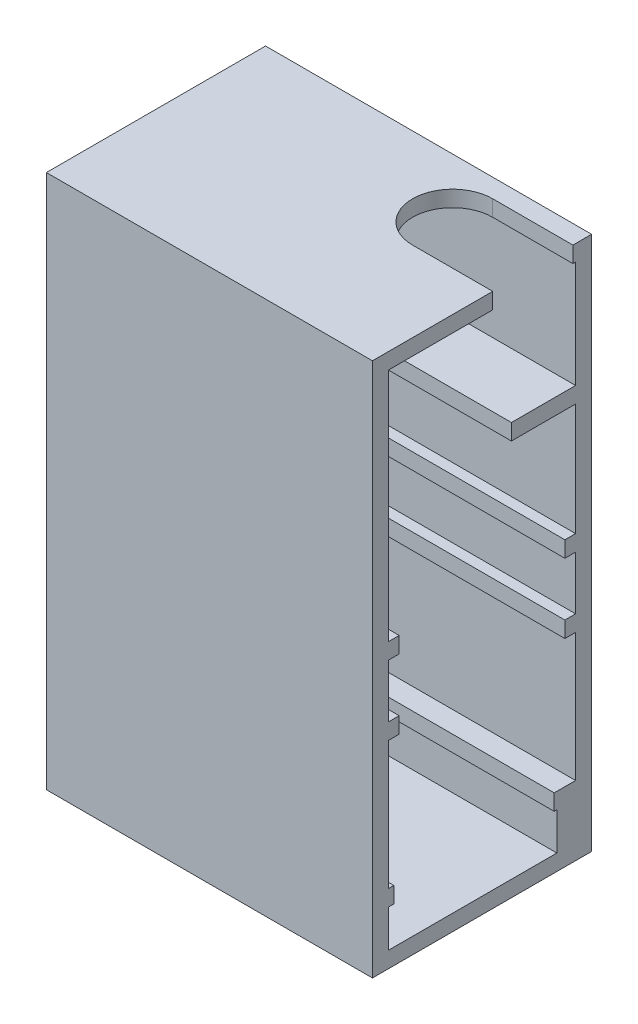
SolidWorks part; units mm, degrees
ref_plane "Plan de face" through (0, 0, 0) normal (0, 0, 1) x (1, 0, 0)
ref_plane "Plan de dessus" through (0, 0, 0) normal (0, 1, 0) x (1, 0, 0)
ref_plane "Plan de droite" through (0, 0, 0) normal (1, 0, 0) x (0, 0, -1)
sketch "Esquisse1" plane through (0, 0, 0) normal (0, 1, 0) x (1, 0, 0)
  line L1 (-30.5, -20.5) -> (30.5, -20.5)
  line L2 (-30.5, -20.5) -> (-30.5, 20.5)
  line L3 (-30.5, 20.5) -> (30.5, 20.5)
  line L4 (30.5, -20.5) -> (30.5, 20.5)
  line L5 (-30.5, -20.5) -> (30.5, 20.5) construction
  line L6 (-30.5, 20.5) -> (30.5, -20.5) construction
  point P0 (0, 0)
  dimension "D1" = 61
  dimension "D2" = 41
extrude "Boss.-Extru.1" add sketch "Esquisse1" along normal blind 100
sketch "Esquisse3" plane through (30.5, 0, 0) normal (1, 0, 0) x (0, 0, -1)
  line L0 (-20.5, 100) -> (20.5, 0) construction
  line L1 (17.5, 13) -> (17.5, 97)
  line L2 (14, 3) -> (-17.5, 3)
  line L4 (17.5, 97) -> (-17.5, 97)
  line L5 (-17.5, 3) -> (-17.5, 97)
  line L6 (17.5, 3) -> (-17.5, 97) construction
  line L7 (17.5, 97) -> (-17.5, 3) construction
  line L8 (-20.5, 100) -> (20.5, 100) construction
  line L14 (17.5, 13) -> (14, 13)
  line L15 (14, 3) -> (14, 13)
  point P4 (0, 50)
  point P5 (0, 50)
  dimension "D1" = 3
  dimension "D3" = 3.5
  dimension "D4" = 10
extrude "Enlèv. mat.-Extru.1" cut sketch "Esquisse3" against normal blind 57 contours L4 L5 L2 L15 L14 L1
sketch "Esquisse6" plane through (0, 0, -20.5) normal (0, 0, -1) x (-1, 0, 0)
  line L0 (-30.5, 100) -> (-30.5, 0) construction
  line L1 (-30.5, 10) -> (27.5, 10)
  line L2 (-30.5, 10) -> (-30.5, 13)
  line L3 (-30.5, 13) -> (27.5, 13)
  line L4 (27.5, 10) -> (27.5, 13)
  line L5 (30.5, 100) -> (30.5, 0) construction
  line L6 (-30.5, 0) -> (30.5, 0) construction
  dimension "D1" = 3
  dimension "D2" = 3
  dimension "D3" = 10
extrude "Boss.-Extru.2" add sketch "Esquisse6" against normal blind 4
mirror "Symétrie1" about plane through (0, 0, 0) normal (0, 0, 1) of "Boss.-Extru.2"
sketch "Esquisse7" plane through (-30.5, 0, 0) normal (-1, 0, 0) x (0, 0, 1)
  line L0 (-20.5, 100) -> (-20.5, 0) construction
  line L1 (-17.5, 10) -> (17.5, 10)
  line L2 (-17.5, 10) -> (-17.5, 13)
  line L3 (-17.5, 13) -> (17.5, 13)
  line L4 (17.5, 10) -> (17.5, 13)
  line L5 (-20.5, 0) -> (20.5, 0) construction
  line L6 (20.5, 100) -> (20.5, 0) construction
  dimension "D1" = 3
  dimension "D2" = 3
  dimension "D3" = 10
  dimension "D4" = 3
extrude "Boss.-Extru.3" add sketch "Esquisse7" against normal blind 6
sketch "Esquisse11" plane through (0, 0, -20.5) normal (0, 0, -1) x (-1, 0, 0)
  line L0 (-30.5, 100) -> (-30.5, 0) construction
  line L1 (-30.5, 10) -> (27.5, 10)
  line L2 (-30.5, 10) -> (-30.5, 13)
  line L3 (-30.5, 13) -> (27.5, 13)
  line L4 (27.5, 10) -> (27.5, 13)
  line L5 (30.5, 100) -> (30.5, 0) construction
  line L6 (-30.5, 0) -> (30.5, 0) construction
  dimension "D1" = 0
  dimension "D2" = 3
  dimension "D3" = 3
  dimension "D4" = 10
extrude "Boss.-Extru.4" add sketch "Esquisse11" against normal blind 7
sketch "Esquisse12" plane through (0, 0, -20.5) normal (0, 0, -1) x (-1, 0, 0)
  line L0 (-30.5, 100) -> (-30.5, 0) construction
  line L1 (-30.5, 50) -> (29.0466, 50)
  line L2 (-30.5, 50) -> (-30.5, 53)
  line L3 (-30.5, 53) -> (29.0466, 53)
  line L4 (29.0466, 50) -> (29.0466, 53)
  line L5 (-30.5, 0) -> (30.5, 0) construction
  dimension "D1" = 3
  dimension "D2" = 50
extrude "Boss.-Extru.5" add sketch "Esquisse12" against normal blind 5
mirror "Symétrie2" about plane through (0, 0, 0) normal (0, 0, 1) of "Boss.-Extru.5"
pattern_linear "Répétition linéaire1" count 2 spacing 13 along (0, -1, 0) of "Symétrie2"
sketch "Esquisse13" plane through (0, 0, 20.5) normal (0, 0, 1) x (1, 0, 0)
  line L0 (-30.5, 100) -> (-30.5, 0) construction
  line L1 (-27.5, 83) -> (-12.5, 83)
  line L2 (-27.5, 83) -> (-27.5, 80)
  line L3 (-27.5, 80) -> (-12.5, 80)
  line L4 (-12.5, 83) -> (-12.5, 80)
  line L5 (-30.5, 100) -> (30.5, 100) construction
  dimension "D1" = 3
  dimension "D2" = 3
  dimension "D3" = 15
  dimension "D4" = 17
extrude "Boss.-Extru.6" add sketch "Esquisse13" against normal blind 5 contours L3 L4 L1 L2
pattern_linear "Répétition linéaire3" count 2 spacing 4 along (0, 1, 0) of "Boss.-Extru.6"
sketch "Esquisse14" plane through (0, 0, -20.5) normal (0, 0, -1) x (-1, 0, 0)
  line L0 (30.5, 100) -> (30.5, 0) construction
  line L1 (27.5, 80) -> (12.5, 80)
  line L2 (27.5, 80) -> (27.5, 87)
  line L3 (27.5, 87) -> (12.5, 87)
  line L4 (12.5, 80) -> (12.5, 87)
  line L6 (-30.5, 100) -> (30.5, 100) construction
  dimension "D1" = 15
  dimension "D2" = 3
  dimension "D3" = 7
  dimension "D4" = 20
extrude "Boss.-Extru.7" add sketch "Esquisse14" against normal blind 16
sketch "Esquisse15" plane through (-12.5, 0, 0) normal (1, 0, 0) x (0, 0, -1)
  line L0 (4.5, 80) -> (4.5, 87) construction
  line L1 (3.5, 83) -> (5.5, 83)
  line L2 (3.5, 83) -> (3.5, 84)
  line L3 (3.5, 84) -> (5.5, 84)
  line L4 (5.5, 83) -> (5.5, 84)
  line L5 (3.5, 83) -> (5.5, 84) construction
  line L6 (3.5, 84) -> (5.5, 83) construction
  point P0 (4.5, 83.5)
  dimension "D1" = 1
  dimension "D2" = 2
extrude "Enlèv. mat.-Extru.2" cut sketch "Esquisse15" against normal up to surface (14 mm away) up to face at (-26.5, 60.6875, 2.75)
sketch "Esquisse16" plane through (0, 100, 0) normal (0, 1, 0) x (1, 0, 0)
  line L1 (30.5, 20.5) -> (-30.5, 20.5) construction
  line L2 (30.5, -20.5) -> (30.5, 20.5) construction
  line L3 (15.5, 2) -> (30.5, 2)
  line L4 (15.5, 17) -> (30.5, 17)
  line L5 (30.5, 2) -> (30.5, 17)
  arc A0 (15.5, 17) -> (15.5, 2) centre (15.5, 9.5) ccw
  dimension "D1" = 15
  dimension "D2" = 15
  dimension "D3" = 11
extrude "Enlèv. mat.-Extru.3" cut sketch "Esquisse16" against normal blind 15
sketch "Esquisse17" plane through (0, 0, -20.5) normal (0, 0, -1) x (-1, 0, 0)
  line L0 (-30.5, 100) -> (-30.5, 0) construction
  line L1 (-30.5, 74) -> (-3.1632, 74)
  line L2 (-30.5, 74) -> (-30.5, 77)
  line L3 (-30.5, 77) -> (-3.1632, 77)
  line L4 (-3.1632, 74) -> (-3.1632, 77)
  line L5 (-30.5, 100) -> (30.5, 100) construction
  dimension "D1" = 3
  dimension "D2" = 23
extrude "Boss.-Extru.8" add sketch "Esquisse17" against normal blind 15
